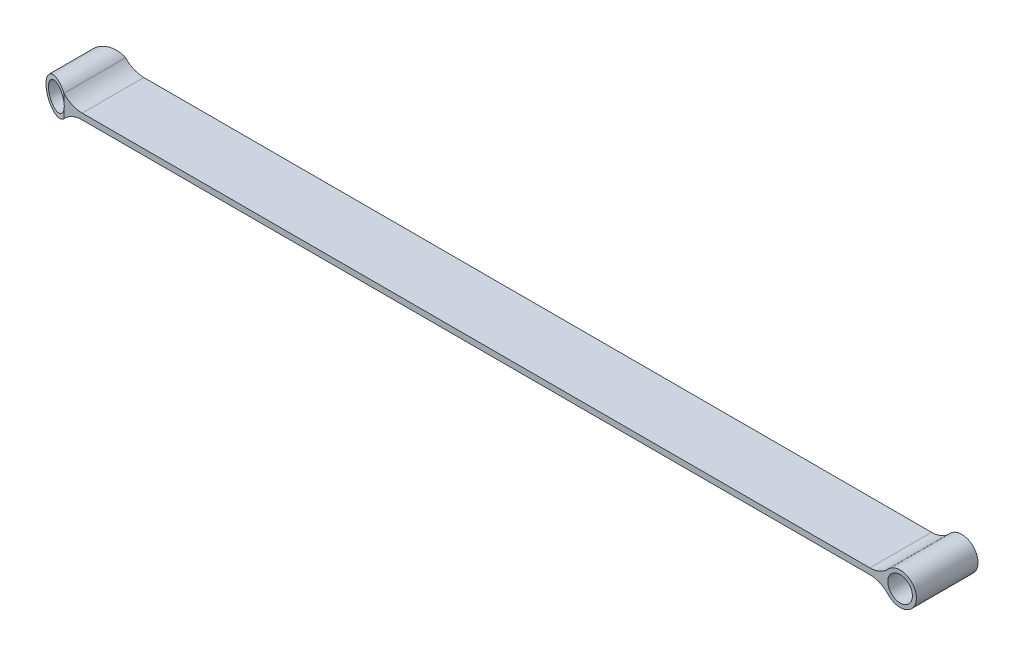
SolidWorks part; units mm, degrees
ref_plane "Front Plane" through (0, 0, 0) normal (0, 0, 1) x (1, 0, 0)
ref_plane "Top Plane" through (0, 0, 0) normal (0, 1, 0) x (1, 0, 0)
ref_plane "Right Plane" through (0, 0, 0) normal (1, 0, 0) x (0, 0, -1)
sketch "Sketch1" plane through (0, 0, 0) normal (0, 1, 0) x (1, 0, 0)
  line L1 (-101.6, -7.9375) -> (101.6, -7.9375)
  line L2 (-101.6, -7.9375) -> (-101.6, 7.9375)
  line L3 (-101.6, 7.9375) -> (101.6, 7.9375)
  line L4 (101.6, -7.9375) -> (101.6, 7.9375)
  line L5 (-101.6, -7.9375) -> (101.6, 7.9375) construction
  line L6 (-101.6, 7.9375) -> (101.6, -7.9375) construction
  point P0 (0, 0)
  dimension "D1" = 15.875
  dimension "D2" = 203.2
extrude "Boss-Extrude1" add sketch "Sketch1" along normal blind 1.524
sketch "Sketch4" plane through (0, 1.524, 0) normal (0, 1, 0) x (1, 0, 0)
  line L0 (-101.6, 7.9375) -> (-101.6, -7.9375) construction
  circle A0 centre (59.563, 0) radius 2.3812
  dimension "D1" = 161.163
  dimension "D2" = 4.7625
sketch "Sketch5" plane through (0, 0, 7.9375) normal (0, 0, 1) x (1, 0, 0)
  line L0 (-101.6, 0) -> (101.6, 0) construction
  line L1 (-101.6, 1.524) -> (101.6, 1.524) construction
  line L2 (-101.4398, 0) -> (101.6, 0)
  line L3 (-101.4398, 1.524) -> (101.6, 1.524)
  line L4 (-101.6, 1.524) -> (-101.6, 0) construction
  line L5 (-101.6, 1.524) -> (-101.6, 0)
  line L6 (101.6, 1.524) -> (101.6, 0)
  line L7 (-101.4398, 1.524) -> (-101.4398, 0)
  circle A0 centre (-109.22, 0.762) radius 3.175
  arc A1 (-106.1267, 3.5897) -> (-106.1267, -2.0657) centre (-109.22, 0.762) ccw
  circle A2 centre (-109.22, 0.762) radius 4.191 construction
  arc A3 (-101.4398, 1.524) -> (-106.1267, 3.5897) centre (-101.4398, 7.874) cw
  arc A4 (-106.1267, -2.0657) -> (-101.4398, 0) centre (-101.4398, -6.35) cw
  point P7 (-101.6, 0.762)
  line M5 (-101.6, 0) -> (101.6, 0)
  line M12 (101.6, 1.524) -> (-101.6, 1.524)
  line M13 (-101.6, 1.524) -> (-101.6, 0)
  dimension "D1" = 6.35
  dimension "D3" = 6.35
  dimension "D4" = 6.35
  dimension "D5" = 7.62
  dimension "D2" = 1.016
extrude "Boss-Extrude5" add sketch "Sketch5" against normal through all contours A1 A4 A3 A0 M5 M13 M12 region at (-104.0597, -0.4056, 7.9375)
mirror "Mirror1" about plane through (0, 0, 0) normal (1, 0, 0) of "Boss-Extrude5"
sketch "Sketch6" plane through (0, 0, 0) normal (0, -1, 0) x (1, 0, 0)
  line L0 (-113.411, 7.9375) -> (-113.411, -7.9375) construction
  line L1 (-113.411, -7.9375) -> (-106.1267, -7.9375) construction
  line L3 (101.4398, -7.9375) -> (-101.4398, -7.9375) construction
  line L4 (-101.4398, 7.9375) -> (101.4398, 7.9375) construction
  line L5 (-101.4398, 7.9375) -> (-106.1267, 7.9375) construction
  line L6 (-106.1267, 7.9375) -> (-113.411, 7.9375) construction
  line L7 (-113.411, 7.9375) -> (-113.411, 5.2862)
  line L8 (-113.411, -7.9375) -> (-106.1267, -7.9375)
  line L9 (-113.411, -7.9375) -> (-113.411, -5.2862)
  line L10 (101.4398, -7.9375) -> (-101.4398, -7.9375)
  line L11 (-101.4398, 7.9375) -> (101.4398, 7.9375)
  line L12 (-101.4398, 7.9375) -> (-106.1267, 7.9375)
  line L13 (-106.1267, 7.9375) -> (-113.411, 7.9375)
  line L14 (-113.411, 5.2862) -> (-106.1267, 7.9375)
  line L16 (-113.411, 0) -> (-106.1267, 0) construction
  line L17 (-106.1267, -7.9375) -> (-106.1267, 7.9375) construction
  line L18 (-106.1267, -7.9375) -> (-113.411, -7.9375)
  line L19 (-113.411, -7.9375) -> (-113.411, -5.2862)
  line L20 (-113.411, -5.2862) -> (-106.1267, -7.9375)
  dimension "D1" = 20
extrude "Cut-Extrude1" cut sketch "Sketch6" against normal through all and the other way through all contours L20 L9 L8 | L7 L14 L13 region at (-110.9829, 0, 7.0537) region at (-110.9829, 0, -7.0537)
